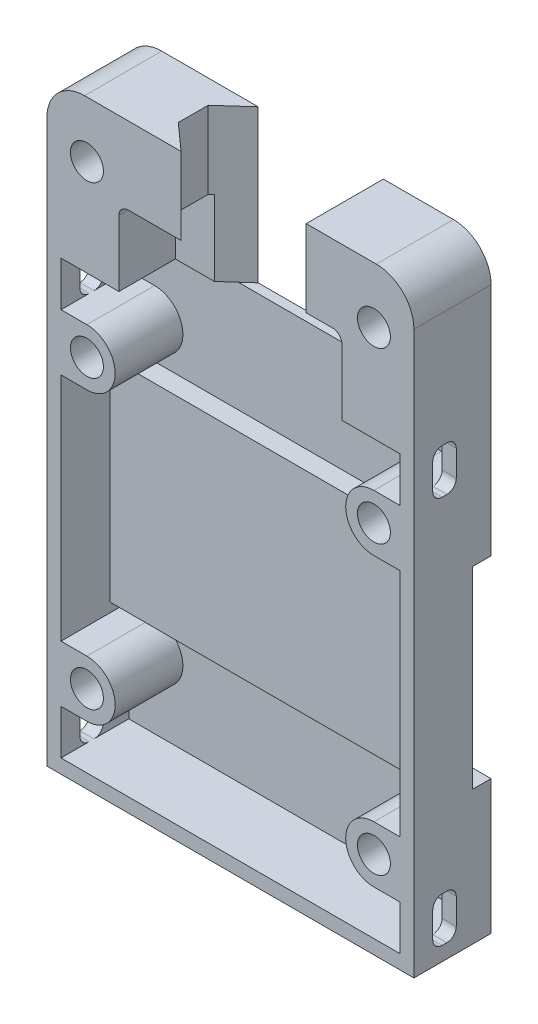
SolidWorks part; units mm, degrees
ref_plane "Front Plane" through (0, 0, 0) normal (0, 0, 1) x (1, 0, 0)
ref_plane "Top Plane" through (0, 0, 0) normal (0, 1, 0) x (1, 0, 0)
ref_plane "Right Plane" through (0, 0, 0) normal (1, 0, 0) x (0, 0, -1)
sketch "Sketch1" plane through (0, 0, 0) normal (0, 0, 1) x (1, 0, 0)
  line L0 (15.25, -20.35) -> (18, -20.35)
  line L1 (-19.5, -32.6) -> (19.5, -32.6)
  line L2 (-19.5, -32.6) -> (-19.5, 31.1)
  line L3 (-19.5, 31.1) -> (19.5, 31.1)
  line L4 (19.5, -32.6) -> (19.5, 31.1)
  line L5 (-15.25, -20.35) -> (-18, -20.35)
  line L6 (15.25, -26.35) -> (18, -26.35)
  line L7 (15.5, 31.1) -> (-15.5, 31.1) construction
  line L8 (-18, -31.1) -> (-18, 29.6)
  line L9 (-18, 29.6) -> (18, 29.6)
  line L10 (18, -31.1) -> (18, 29.6)
  line L11 (-18, -31.1) -> (18, -31.1)
  line L12 (-18, 14.9) -> (18, 14.9)
  line L13 (7.85, 14.9) -> (-4.95, 14.9) construction
  line L14 (-15.25, 4.15) -> (-18, 4.15)
  line L15 (-15.25, 10.15) -> (-18, 10.15)
  line L16 (15.25, 10.15) -> (18, 10.15)
  line L17 (15.25, 4.15) -> (18, 4.15)
  line L18 (-15.25, -26.35) -> (-18, -26.35)
  arc A0 (19.5, 27.1) -> (15.5, 31.1) centre (15.5, 27.1) ccw construction
  arc A1 (-15.5, 31.1) -> (-19.5, 27.1) centre (-15.5, 27.1) ccw construction
  arc A2 (19.5, 27.1) -> (15.5, 31.1) centre (15.5, 27.1) ccw
  arc A3 (-15.5, 31.1) -> (-19.5, 27.1) centre (-15.5, 27.1) ccw
  arc A4 (-15.5, 29.6) -> (-18, 27.1) centre (-15.5, 27.1) ccw
  arc A5 (18, 27.1) -> (15.5, 29.6) centre (15.5, 27.1) ccw
  circle A6 centre (-15.25, -23.35) radius 1.75
  circle A7 centre (15.25, -23.35) radius 1.75
  circle A8 centre (-15.25, 7.15) radius 1.75
  circle A9 centre (15.25, 7.15) radius 1.75
  circle A10 centre (15.25, 25.15) radius 1.75
  circle A11 centre (-15.25, 25.15) radius 1.75
  circle A12 centre (-15.25, -23.35) radius 3
  circle A13 centre (15.25, -23.35) radius 3
  circle A14 centre (15.25, 7.15) radius 3
  circle A15 centre (-15.25, 7.15) radius 3
  dimension "D2" = 1.5
  dimension "D4" = 6
  dimension "D3" = 3.5
  dimension "D1" = 1.5
extrude "Base shape" add sketch "Sketch1" along normal up to surface (8.2 mm away) contours L10 A5 L9 A4 L8 L12 A11 A10 | L3 A3 L2 L1 L4 A2 A15 L8 L9 L10 A14 A13 L11 A12 | A4 L9 L8 | A5 L10 L9 | A15 L15 L8 | A15 L8 A8 | A15 L8 L14 | L8 A15 | A14 L17 L10 | L10 A14 A9 | L10 A14 | A14 L10 L16 | A13 L6 L10 | L10 A13 A7 | L10 A13 | A13 L10 L0 | A12 L8 L18 | A12 L8 A6 | L8 A12 | A12 L5 L8 region at (16.8481, -20.9099, 0) region at (17.3601, -20.8437, 0) region at (17.3601, -25.8563, 0) region at (18.1004, -23.35, 0) region at (17.3601, 4.6437, 0) region at (16.8481, 4.7099, 0) region at (18.1004, 7.15, 0) region at (17.3601, 9.6563, 0) region at (-17.3601, -25.8563, 0) region at (0, 22.1041, 0) region at (-18.1004, -23.35, 0) region at (-17.9169, -23.35, 0) region at (17.4416, 29.0416, 0) region at (-17.3601, -20.8437, 0) region at (-17.3601, 9.6563, 0) region at (-17.4416, 29.0416, 0) region at (-16.8481, 9.5901, 0) region at (-18.1004, 7.15, 0) region at (-17.3601, 4.6437, 0) region at (-18.7531, -2.75, 0)
sketch "Sketch3" plane through (19.5, 0, 0) normal (1, 0, 0) x (0, 0, -1)
  line L1 (0, -18.35) -> (-2, -18.35)
  line L2 (0, -18.35) -> (0, 2.15)
  line L3 (0, 2.15) -> (-2, 2.15)
  line L4 (-2, -18.35) -> (-2, 2.15)
  line L5 (0, -18.35) -> (2, -18.35) construction
  line L6 (0, 2.15) -> (2, 2.15) construction
  line L7 (0, -32.6) -> (0, 27.1) construction
  dimension "D1" = 2
extrude "Strap cut" cut sketch "Sketch3" against normal through all
sketch "Sketch4" plane through (0, 31.1, 0) normal (0, 1, 0) x (1, 0, 0)
  line L2 (8.05, 0) -> (-5.2496, 0)
  line L4 (-15.5, 0) -> (15.5, 0) construction
  line L5 (-15.5, -8.2) -> (15.5, -8.2) construction
  line L6 (8.05, -8.2) -> (-5.2496, -8.2)
  line L12 (8.05, -8.4) -> (8.05, 0.2)
  line L13 (8.05, 0.2) -> (-5.0265, 0.2)
  line L14 (-5.0265, 0.2) -> (-8.05, -2.5107)
  line L15 (-8.05, -2.5107) -> (-8.05, -5.6893)
  line L16 (-8.05, -5.6893) -> (-5.0265, -8.4)
  line L17 (-5.0265, -8.4) -> (8.05, -8.4)
  line L18 (8.05, -8.4) -> (8.05, 0.2)
  line L19 (8.05, 0.2) -> (-5.0265, 0.2)
  line L20 (-5.0265, 0.2) -> (-8.05, -2.5107)
  line L21 (-8.05, -2.5107) -> (-8.05, -5.6893)
  line L22 (-8.05, -5.6893) -> (-5.0265, -8.4)
  line L23 (-5.0265, -8.4) -> (8.05, -8.4)
  dimension "D1" = 0.2
extrude "XT60 cut" cut sketch "Sketch4" against normal up to next contours L21 L22 L18 L20 region at (0.4003, 31.1, 4.1)
sketch "Sketch5" plane through (19.5, 0, 0) normal (1, 0, 0) x (0, 0, -1)
  line L0 (-8.2, -32.6) -> (-8.2, 27.1) construction
  line L2 (-5.2, -31.1) -> (-4.7, -31.1)
  line L3 (-6.2, -30.1) -> (-6.2, -27.35)
  line L4 (-5.2, -26.35) -> (-4.7, -26.35)
  line L5 (-3.7, -30.1) -> (-3.7, -27.35)
  line L8 (-5.2, 14.9) -> (-4.7, 14.9)
  line L9 (-6.2, 13.9) -> (-6.2, 11.15)
  line L10 (-5.2, 10.15) -> (-4.7, 10.15)
  line L11 (-3.7, 13.9) -> (-3.7, 11.15)
  line L12 (-8.2, 14.9) -> (0, 14.9) construction
  line L13 (-8.2, 10.15) -> (0, 10.15) construction
  arc A0 (-4.7, 14.9) -> (-3.7, 13.9) centre (-4.7, 13.9) cw
  arc A1 (-5.2, 14.9) -> (-6.2, 13.9) centre (-5.2, 13.9) ccw
  arc A2 (-4.7, 10.15) -> (-3.7, 11.15) centre (-4.7, 11.15) ccw
  arc A3 (-6.2, 11.15) -> (-5.2, 10.15) centre (-5.2, 11.15) ccw
  arc A4 (-5.2, -31.1) -> (-6.2, -30.1) centre (-5.2, -30.1) cw
  arc A5 (-4.7, -31.1) -> (-3.7, -30.1) centre (-4.7, -30.1) ccw
  arc A6 (-4.7, -26.35) -> (-3.7, -27.35) centre (-4.7, -27.35) cw
  arc A7 (-6.2, -27.35) -> (-5.2, -26.35) centre (-5.2, -27.35) cw
  point P8 (0, 0)
  point P26 (-6.2, -31.1)
  point P29 (-3.7, -31.1)
  dimension "D3" = 1
  dimension "D1" = 2
  dimension "D2" = 2.5
extrude "Power wires cut" cut sketch "Sketch5" against normal through all
sketch "Sketch6" plane through (0, 0, 8.2) normal (0, 0, 1) x (1, 0, 0)
  line L0 (-7.85, 15.9) -> (-7.85, 21.9) construction
  line L1 (-8.85, 22.9) -> (-10.85, 22.9) construction
  line L2 (-11.85, 15.9) -> (-11.85, 21.9) construction
  line L3 (-8.85, 14.9) -> (-10.85, 14.9) construction
  line L4 (-7.85, 15.9) -> (-7.85, 21.9)
  line L5 (-8.85, 22.9) -> (-10.85, 22.9)
  line L6 (-11.85, 15.9) -> (-11.85, 21.9)
  line L7 (-8.85, 14.9) -> (-10.85, 14.9)
  line L8 (7.85, 15.9) -> (7.85, 21.9) construction
  line L9 (8.85, 22.9) -> (10.85, 22.9) construction
  line L10 (11.85, 15.9) -> (11.85, 21.9) construction
  line L11 (8.85, 14.9) -> (10.85, 14.9) construction
  line L12 (7.85, 15.9) -> (7.85, 21.9)
  line L13 (8.85, 22.9) -> (10.85, 22.9)
  line L14 (11.85, 15.9) -> (11.85, 21.9)
  line L15 (8.85, 14.9) -> (10.85, 14.9)
  line L17 (-11.85, 15.9) -> (-7.85, 15.9)
  line L18 (-11.85, 15.9) -> (-11.85, 14.9)
  line L19 (-11.85, 14.9) -> (-7.85, 14.9)
  line L20 (-7.85, 15.9) -> (-7.85, 14.9)
  line L22 (11.85, 15.9) -> (7.85, 15.9)
  line L23 (11.85, 15.9) -> (11.85, 14.9)
  line L24 (11.85, 14.9) -> (7.85, 14.9)
  line L25 (7.85, 15.9) -> (7.85, 14.9)
  line L26 (-18, 14.9) -> (-5.2496, 14.9) construction
  line L27 (11.85, 21.9) -> (7.85, 21.9)
  line L28 (11.85, 21.9) -> (11.85, 22.9)
  line L29 (11.85, 22.9) -> (7.85, 22.9)
  line L30 (7.85, 21.9) -> (7.85, 22.9)
  line L31 (-8.85, 22.9) -> (8.05, 22.9)
  line L32 (-8.85, 22.9) -> (-8.85, 14.9)
  line L33 (-8.85, 14.9) -> (8.05, 14.9)
  line L34 (8.05, 22.9) -> (8.05, 14.9)
  line L35 (8.05, 14.9) -> (18, 14.9) construction
  line L36 (8.05, 14.9) -> (8.05, 31.1) construction
  arc A0 (-8.85, 14.9) -> (-7.85, 15.9) centre (-8.85, 15.9) ccw construction
  arc A1 (-7.85, 21.9) -> (-8.85, 22.9) centre (-8.85, 21.9) ccw construction
  arc A2 (-10.85, 22.9) -> (-11.85, 21.9) centre (-10.85, 21.9) ccw construction
  arc A3 (-11.85, 15.9) -> (-10.85, 14.9) centre (-10.85, 15.9) ccw construction
  arc A4 (-8.85, 14.9) -> (-7.85, 15.9) centre (-8.85, 15.9) ccw
  arc A5 (-7.85, 21.9) -> (-8.85, 22.9) centre (-8.85, 21.9) ccw
  arc A6 (-10.85, 22.9) -> (-11.85, 21.9) centre (-10.85, 21.9) ccw
  arc A7 (-11.85, 15.9) -> (-10.85, 14.9) centre (-10.85, 15.9) ccw
  arc A8 (8.85, 22.9) -> (7.85, 21.9) centre (8.85, 21.9) ccw construction
  arc A9 (11.85, 21.9) -> (10.85, 22.9) centre (10.85, 21.9) ccw construction
  arc A10 (10.85, 14.9) -> (11.85, 15.9) centre (10.85, 15.9) ccw construction
  arc A11 (7.85, 15.9) -> (8.85, 14.9) centre (8.85, 15.9) ccw construction
  arc A12 (8.85, 22.9) -> (7.85, 21.9) centre (8.85, 21.9) ccw
  arc A13 (11.85, 21.9) -> (10.85, 22.9) centre (10.85, 21.9) ccw
  arc A14 (10.85, 14.9) -> (11.85, 15.9) centre (10.85, 15.9) ccw
  arc A15 (7.85, 15.9) -> (8.85, 14.9) centre (8.85, 15.9) ccw
  line M1 (8.05, 31.1) -> (8.05, 14.9)
  line M15 (-5.2496, 14.9) -> (-5.2496, 31.1)
extrude "IO wires cut" cut sketch "Sketch6" against normal blind 6 contours L33 L25 L12 L30 L31 M15 | A5 L4 L20 L31 M15 | L4 A5 L32 L17 | L5 A6 L6 L17 L32 | A7 L18 | L17 A7 L32 | L32 A4 L17 | A4 L20 | A12 L29 L30 M1 | L27 L12 L22 M1 | L22 A15 M1 | A15 L25 L24 L34 | A15 L34 | A15 A14 L22 M1 | A14 L23 | L14 L27 L22 M1 | L27 A13 L13 A12 L34 | A12 L29 M1 region at (-8.3587, 19.2964, 8.2) region at (-8.4256, 15.4756, 8.2) region at (-6.5654, 18.9386, 8.2) region at (-8.0734, 15.1234, 8.2) region at (-10.2516, 15.4213, 8.2) region at (-10.3368, 19.3662, 8.2) region at (-11.6266, 15.1234, 8.2) region at (1.3002, 18.9, 8.2) region at (7.9367, 15.2122, 8.2) region at (7.9367, 22.5878, 8.2) region at (8.2411, 15.0144, 8.2) region at (7.95, 18.9, 8.2) region at (7.9693, 15.6717, 8.2) region at (8.2411, 22.7856, 8.2) region at (9.8941, 15.4277, 8.2) region at (9.95, 18.9, 8.2) region at (9.8941, 22.3723, 8.2) region at (11.6266, 15.1234, 8.2)
sketch "Sketch7" plane through (-18, 0, 0) normal (1, 0, 0) x (0, 0, -1)
  line L6 (0, -18.35) -> (0, -20.35)
  line L7 (-2, -18.35) -> (0, -18.35)
  line L8 (-2, 2.15) -> (-2, -18.35)
  line L9 (0, 2.15) -> (-2, 2.15)
  line L12 (0, 3.15) -> (-3, 3.15)
  line L13 (-3, 3.15) -> (-3, -19.35)
  line L14 (-3, -19.35) -> (-1, -19.35)
  line L15 (-1, -19.35) -> (-1, -20.35)
  line L16 (-1, -20.35) -> (0, -20.35)
  line L17 (0, 3.15) -> (-1, 3.15)
  line L19 (0, -31.1) -> (-1, -31.1)
  line L22 (0, -31.1) -> (0, -20.35)
  line L23 (0, -20.35) -> (-1, -20.35)
  line L24 (-1, -31.1) -> (-1, -20.35)
  line L25 (0, 3.15) -> (0, 14.9)
  line L26 (0, 14.9) -> (-1, 14.9)
  line L27 (-1, 3.15) -> (-1, 14.9)
  line L28 (-4.7, 14.9) -> (0, 14.9) construction
  line L31 (0, -20.35) -> (0, -18.35) construction
  line L32 (0, 2.15) -> (-2, 2.15) construction
  point P17 (0, -18.7125)
  point P19 (0, 0)
  point P20 (0, 0)
  point P22 (0, 0)
  point P23 (0, 0)
  point P29 (0, 0)
  point P31 (-0.3704, 2.31)
  point P34 (0, -19.9339)
  point P36 (0, 0)
  line M48 (0, -20.35) -> (0, -18.35)
  line M49 (0, -18.35) -> (-2, -18.35)
  line M50 (-2, -18.35) -> (-2, 2.15)
  line M51 (-2, 2.15) -> (0, 2.15)
  line M52 (0, 2.15) -> (0, 4.15)
  line M53 (0, 4.15) -> (-8.2, 4.15)
  line M55 (-8.2, -20.35) -> (0, -20.35)
  dimension "D1" = 1
extrude "Bottom" add sketch "Sketch7" along normal up to surface (36 mm away) contours L27 L25 L26 M53 | L27 L12 M52 M53 | L14 L15 L12 L13 M55 M48 M49 M50 M51 M52 | L24 L19 L22 M55 region at (-18, -8.5273, 2.2091) region at (-18, -25.725, 0.5) region at (-18, 3.65, 0.5) region at (-18, 9.525, 0.5) up to face at (18, -8.1, 2.55)
